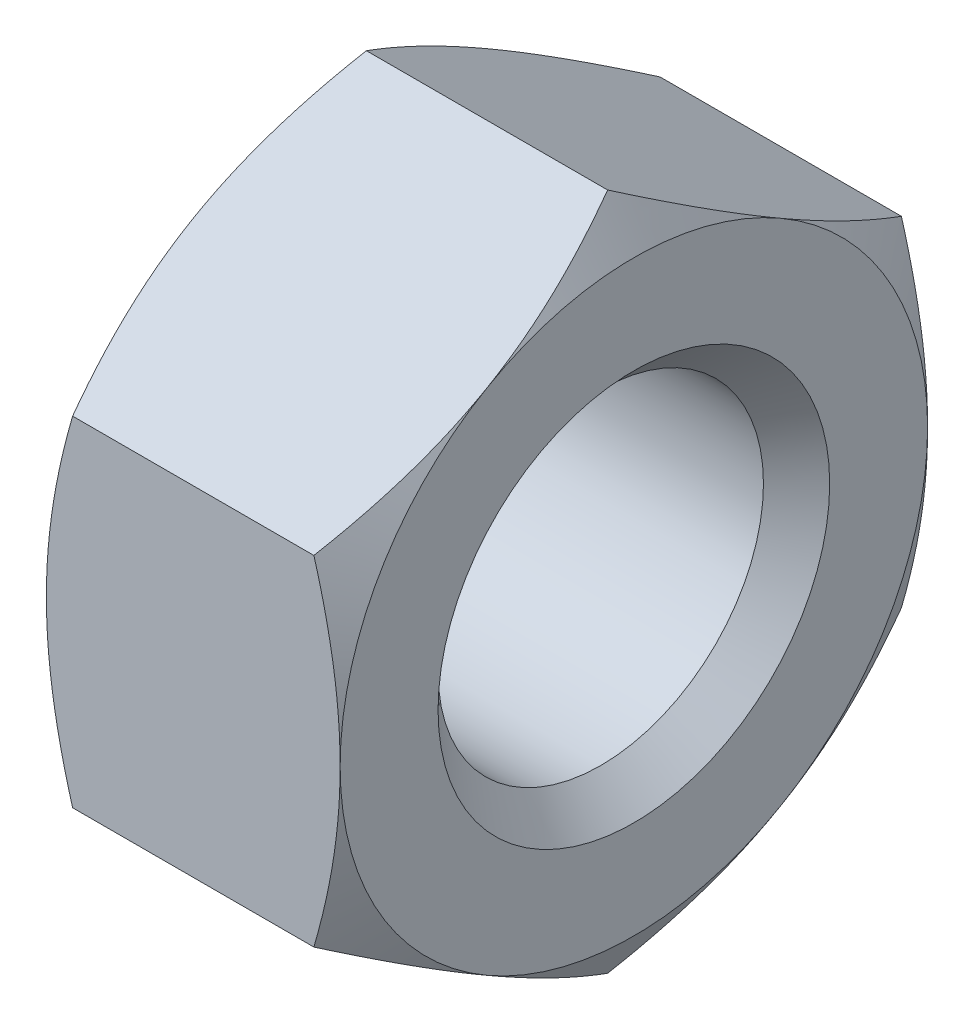
SolidWorks part; units mm, degrees
ref_plane "前视基准面" through (0, 0, 0) normal (0, 0, 1) x (1, 0, 0)
ref_plane "上视基准面" through (0, 0, 0) normal (0, 1, 0) x (1, 0, 0)
ref_plane "右视基准面" through (0, 0, 0) normal (1, 0, 0) x (0, 0, -1)
sketch "草图1" plane through (0, 0, 0) normal (0, 0, 1) x (1, 0, 0)
  line L0 (-3, 0) -> (-3, 6)
  line L1 (-3, 6) -> (-2.3072, 7.2)
  line L2 (-2.3072, 7.2) -> (2.3072, 7.2)
  line L3 (2.3072, 7.2) -> (3, 6)
  line L4 (3, 6) -> (3, 0)
  line L5 (3, 0) -> (-3, 0)
  line L6 (3, 0) -> (-3, 0) construction
revolve "旋转1" add sketch "草图1" angle 360 about L6 reverse direction yes
sketch "草图2" plane through (0, 0, 0) normal (0, 0, 1) x (1, 0, 0)
  line L0 (-3, 0) -> (-3, 4)
  line L1 (-3, 4) -> (-2.3235, 3.3235)
  line L2 (-2.3235, 3.3235) -> (2.3235, 3.3235)
  line L3 (2.3235, 3.3235) -> (3, 4)
  line L4 (3, 4) -> (3, 0)
  line L5 (3, 0) -> (-3, 0)
  line L6 (3, 0) -> (-3, 0) construction
revolve "切除-旋转1" cut sketch "草图2" angle 360 about L6 reverse direction yes
cosmetic thread "装饰螺纹线1" parameters "D1"=6, "D2"=8
sketch "草图3" plane through (0, 0, 0) normal (1, 0, 0) x (0, 0, -1)
  line L0 (-12, 12) -> (-12, -12)
  line L1 (-12, -12) -> (12, -12)
  line L2 (12, -12) -> (12, 12)
  line L3 (12, 12) -> (-12, 12)
  line L4 (-6, -3.4641) -> (0, -6.9282)
  line L5 (0, -6.9282) -> (6, -3.4641)
  line L6 (6, -3.4641) -> (6, 3.4641)
  line L7 (6, 3.4641) -> (0, 6.9282)
  line L8 (0, 6.9282) -> (-6, 3.4641)
  line L9 (-6, 3.4641) -> (-6, -3.4641)
extrude "切除-拉伸1" cut sketch "草图3" along normal blind 3 and the other way blind 3
ref_plane "nut1 XY" through (0, 0, 0) normal (-1, 0, 0) x (0, 0, 1)
ref_plane "nut1 XZ" through (0, 0, 0) normal (0, 1, 0) x (1, 0, 0)
ref_plane "nut1 YZ" through (0, 0, 0) normal (0, 0, -1) x (-1, 0, 0)
ref_axis "nut1 X" through (0, 0, 80.9) along (0, 0, -1)
ref_axis "nut1 Y" through (0, 50, 0) along (0, -1, 0)
ref_axis "nut1 Z" through (-80.9, 0, 0) along (1, 0, 0)
sketch3d "nut1"
  point P0 (0, 0, 0)
